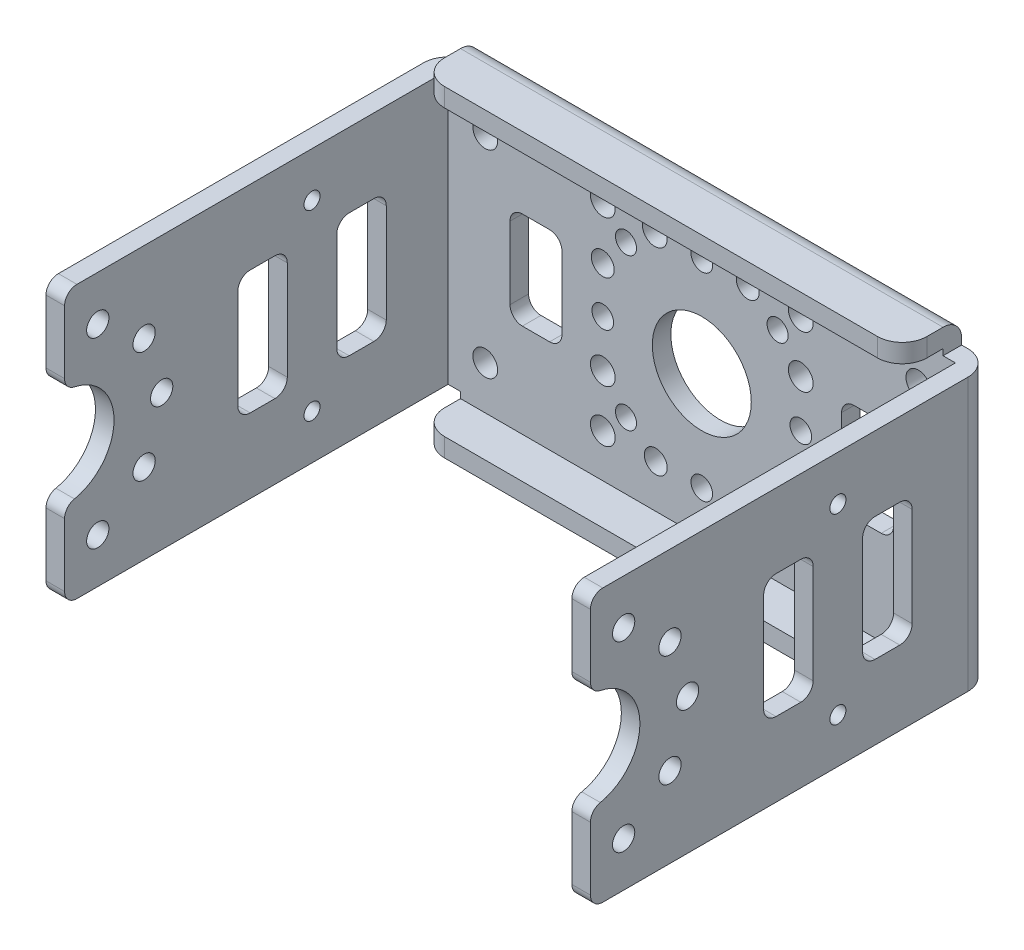
SolidWorks part; units mm, degrees
material "1060 Alloy"
ref_plane "Front Plane" through (0, 0, 0) normal (0, 0, 1) x (1, 0, 0)
ref_plane "Top Plane" through (0, 0, 0) normal (0, 1, 0) x (1, 0, 0)
ref_plane "Right Plane" through (0, 0, 0) normal (1, 0, 0) x (0, 0, -1)
sketch "Sketch1" plane through (0, 0, 0) normal (0, 0, 1) x (1, 0, 0)
  line L0 (-8, 8) -> (-8, -8) construction
  line L1 (-19.5, 13) -> (19.5, 13)
  line L2 (-19.5, 13) -> (-19.5, -13)
  line L3 (-19.5, -13) -> (19.5, -13)
  line L4 (19.5, 13) -> (19.5, -13)
  line L5 (-19.5, 13) -> (19.5, -13) construction
  line L6 (-19.5, -13) -> (19.5, 13) construction
  line L7 (-9, -9) -> (9, -9) construction
  line L8 (-9, -9) -> (-9, 9) construction
  line L9 (-9, 9) -> (9, 9) construction
  line L10 (9, -9) -> (9, 9) construction
  line L11 (-9, -9) -> (9, 9) construction
  line L12 (-9, 9) -> (9, -9) construction
  line L13 (-19.5, 0) -> (19.5, 0) construction
  line L14 (0, 13) -> (0, -13) construction
  line L15 (12.3, 3.925) -> (14.5, 3.925)
  line L16 (11.3, 2.925) -> (11.3, -2.925)
  line L17 (12.3, -3.925) -> (14.5, -3.925)
  line L18 (15.5, 2.925) -> (15.5, -2.925)
  line L19 (11.3, 3.925) -> (15.5, -3.925) construction
  line L20 (11.3, -3.925) -> (15.5, 3.925) construction
  line L21 (-18.5, -9) -> (18.5, -9) construction
  line L22 (-18.5, -9) -> (-18.5, 9) construction
  line L23 (-18.5, 9) -> (18.5, 9) construction
  line L24 (18.5, -9) -> (18.5, 9) construction
  line L25 (-18.5, -9) -> (18.5, 9) construction
  line L26 (-18.5, 9) -> (18.5, -9) construction
  line L27 (-12.3, 3.925) -> (-14.5, 3.925)
  line L28 (-15.5, 2.925) -> (-15.5, -2.925)
  line L29 (-11.3, 2.925) -> (-11.3, -2.925)
  line L30 (-12.3, -3.925) -> (-14.5, -3.925)
  circle A0 centre (0, 0) radius 4
  circle A1 centre (-8, 8) radius 1
  circle A2 centre (-8, -8) radius 1
  circle A3 centre (-8, -3.8) radius 1
  circle A4 centre (-8, 0) radius 0.875
  circle A5 centre (-8, 3.72) radius 0.925
  circle A6 centre (8, 8) radius 1
  circle A7 centre (3.72, 8) radius 0.925
  circle A8 centre (0, 8) radius 0.875
  circle A9 centre (-3.8, 8) radius 1
  circle A10 centre (-8, 8) radius 1
  circle A11 centre (8, -8) radius 1
  circle A12 centre (8, -3.72) radius 0.925
  circle A13 centre (8, 0) radius 0.875
  circle A14 centre (8, 3.8) radius 1
  circle A15 centre (8, 8) radius 1
  circle A16 centre (-8, -8) radius 1
  circle A17 centre (-3.72, -8) radius 0.925
  circle A18 centre (0, -8) radius 0.875
  circle A19 centre (3.8, -8) radius 1
  circle A20 centre (8, -8) radius 1
  circle A21 centre (6.1262, 6.1262) radius 0.85
  circle A22 centre (6.1262, -6.1262) radius 0.85
  circle A23 centre (-6.1262, -6.1262) radius 0.85
  circle A24 centre (-6.1262, 6.1262) radius 0.85
  arc A25 (11.3, -2.925) -> (12.3, -3.925) centre (12.3, -2.925) ccw
  arc A26 (14.5, -3.925) -> (15.5, -2.925) centre (14.5, -2.925) ccw
  arc A27 (12.3, 3.925) -> (11.3, 2.925) centre (12.3, 2.925) ccw
  arc A28 (14.5, 3.925) -> (15.5, 2.925) centre (14.5, 2.925) cw
  circle A29 centre (17.5, 8) radius 1
  circle A30 centre (17.5, -8) radius 1
  arc A31 (-12.3, 3.925) -> (-11.3, 2.925) centre (-12.3, 2.925) cw
  arc A32 (-14.5, 3.925) -> (-15.5, 2.925) centre (-14.5, 2.925) ccw
  arc A33 (-11.3, -2.925) -> (-12.3, -3.925) centre (-12.3, -2.925) cw
  arc A34 (-14.5, -3.925) -> (-15.5, -2.925) centre (-14.5, -2.925) cw
  circle A35 centre (-17.5, -8) radius 1
  circle A36 centre (-17.5, 8) radius 1
  point P0 (0, 0)
  point P6 (0, 0)
  point P56 (0, 0)
  point P58 (13.4, 0)
  point P65 (0, 0)
  point P98 (-15.5, 3.925)
  point P103 (-11.3, -3.925)
  dimension "D4" = 2
  dimension "D5" = 2
  dimension "D7" = 2
  dimension "D8" = 1.75
  dimension "D9" = 1.85
  dimension "D12" = 1.7
  dimension "D18" = 1
  dimension "D21" = 2
  dimension "D1" = 39
  dimension "D2" = 26
  dimension "D3" = 18
  dimension "D6" = 4.2
  dimension "D10" = 4.28
  dimension "D13" = 2.65
  dimension "D15" = 2.3
  dimension "D16" = 4.2
  dimension "D17" = 7.85
  dimension "D19" = 37
  dimension "D20" = 18
  dimension "D11" = 4
  dimension "D14" = 4
extrude "Boss-Extrude1" add sketch "Sketch1" along normal blind 1.5 contours L4 L1 L2 L3 L30 A34 L28 A32 L27 A31 L29 A33 L15 A28 L18 A26 L17 A25 L16 A27 A24 A23 A22 A21 A19 A18 A17 A14 A13 A12 A11 A9 A8 A7 region at (0, 12.5313, 0)
sketch "Sketch2" plane through (-19.5, 0, 0) normal (-1, 0, 0) x (0, 0, 1)
  line L0 (0, 13) -> (0, -13) construction
  line L1 (0, 11) -> (1.5, 11)
  line L2 (0, 11) -> (0, -11)
  line L3 (0, -11) -> (1.5, -11)
  line L4 (1.5, 11) -> (1.5, -11)
  line L5 (1.5, 13) -> (0, 13) construction
  dimension "D1" = 1.5
  dimension "D2" = 22
  dimension "D3" = 2
extrude "Boss-Extrude2" add sketch "Sketch2" along normal blind 1
sketch "Sketch3" plane through (-20.5, 0, 0) normal (-1, 0, 0) x (0, 0, 1)
  line L0 (0, 0) -> (32.5, 0) construction
  line L1 (0, 11) -> (32.5, 11)
  line L2 (0, 11) -> (0, -11)
  line L3 (0, -11) -> (32.5, -11)
  line L4 (32.5, 11) -> (32.5, 4)
  line L5 (32.5, -4) -> (32.5, -11)
  line L6 (32.5, 0) -> (24.65, 0) construction
  line L7 (32.5, 0) -> (26.0697, 4.5026) construction
  line L8 (12.5, 11) -> (12.5, -11) construction
  line L9 (15.5, -5) -> (17.5, -5)
  line L10 (14.5, -4) -> (14.5, 4)
  line L11 (15.5, 5) -> (17.5, 5)
  line L12 (18.5, -4) -> (18.5, 4)
  line L13 (14.5, -5) -> (18.5, 5) construction
  line L14 (14.5, 5) -> (18.5, -5) construction
  line L15 (7.5, 5) -> (9.5, 5)
  line L16 (6.5, 4) -> (6.5, -4)
  line L17 (7.5, -5) -> (9.5, -5)
  line L18 (10.5, 4) -> (10.5, -4)
  line L19 (6.5, 5) -> (10.5, -5) construction
  line L20 (6.5, -5) -> (10.5, 5) construction
  line L21 (29.8151, 7.3766) -> (12.5, 7.3766) construction
  arc A0 (32.5, 4) -> (32.5, -4) centre (32.5, 0) ccw
  arc A1 (32.5, 7.85) -> (32.5, -7.85) centre (32.5, 0) ccw construction
  circle A2 centre (24.65, 0) radius 0.9
  circle A3 centre (26.0697, 4.5026) radius 0.9
  circle A4 centre (29.8151, 7.3766) radius 0.9
  circle A5 centre (29.8151, -7.3766) radius 0.9
  circle A6 centre (26.0697, -4.5026) radius 0.9
  arc A7 (15.5, -5) -> (14.5, -4) centre (15.5, -4) cw
  arc A8 (17.5, -5) -> (18.5, -4) centre (17.5, -4) ccw
  arc A9 (17.5, 5) -> (18.5, 4) centre (17.5, 4) cw
  arc A10 (14.5, 4) -> (15.5, 5) centre (15.5, 4) cw
  arc A11 (6.5, -4) -> (7.5, -5) centre (7.5, -4) ccw
  arc A12 (9.5, -5) -> (10.5, -4) centre (9.5, -4) ccw
  arc A13 (9.5, 5) -> (10.5, 4) centre (9.5, 4) cw
  arc A14 (7.5, 5) -> (6.5, 4) centre (7.5, 4) ccw
  circle A15 centre (12.5, 7.3766) radius 0.65
  circle A16 centre (12.5, -7.3766) radius 0.65
  point P25 (16.5, 0)
  point P42 (8.5, 0)
  dimension "D2" = 3
  dimension "D7" = 1
  dimension "D11" = 1
  dimension "D1" = 32.5
  dimension "D3" = 35
  dimension "D4" = 14
  dimension "D5" = 4
  dimension "D6" = 10
  dimension "D8" = 4
  dimension "D9" = 10
  dimension "D10" = 4
  dimension "D12" = 2
extrude "Boss-Extrude3" add sketch "Sketch3" along normal blind 1.5
fillet "Fillet1" radius 2 1 edges at (-22, 0, 0)
fillet "Fillet2" radius 1 4 edges at (-21.25, 11, 32.5) (-21.25, 4, 32.5) (-21.25, -4, 32.5) (-21.25, -11, 32.5)
mirror "Mirror1" about plane through (0, 0, 0) normal (1, 0, 0) of "Fillet2", "Fillet1", "Boss-Extrude3", "Boss-Extrude2"
sketch "Sketch4" plane through (0, 13, 0) normal (0, 1, 0) x (1, 0, 0)
  line L1 (-19.5, 0) -> (19.5, 0)
  line L2 (-19.5, 0) -> (-19.5, -4.8)
  line L3 (-19.5, -4.8) -> (19.5, -4.8)
  line L4 (19.5, 0) -> (19.5, -4.8)
  dimension "D1" = 39
  dimension "D2" = 4.8
extrude "Boss-Extrude4" add sketch "Sketch4" against normal blind 1.5
fillet "Fillet3" radius 2 2 edges at (19.5, 12.25, 4.8) (-19.5, 12.25, 4.8)
fillet "Fillet4" radius 1.5 1 edges at (0, 13, 0)
sketch "Sketch5" plane through (0, -13, 0) normal (0, -1, 0) x (1, 0, 0)
  line L1 (-19.5, 0) -> (19.5, 0)
  line L2 (-19.5, 0) -> (-19.5, 4.8)
  line L3 (-19.5, 4.8) -> (19.5, 4.8)
  line L4 (19.5, 0) -> (19.5, 4.8)
  dimension "D1" = 4.8
extrude "Boss-Extrude5" add sketch "Sketch5" against normal blind 1.5
fillet "Fillet5" radius 2 2 edges at (-19.5, -12.25, 4.8) (19.5, -12.25, 4.8)
fillet "Fillet6" radius 1.5 1 edges at (0, -13, 0)
ref_axis "head_p_axis" through (0, 0, 13.3779) along (0, 0, -1)
ref_axis "Axis2" through (22, 0, 32.5) along (-1, 0, 0)
ref_point "Point1"
